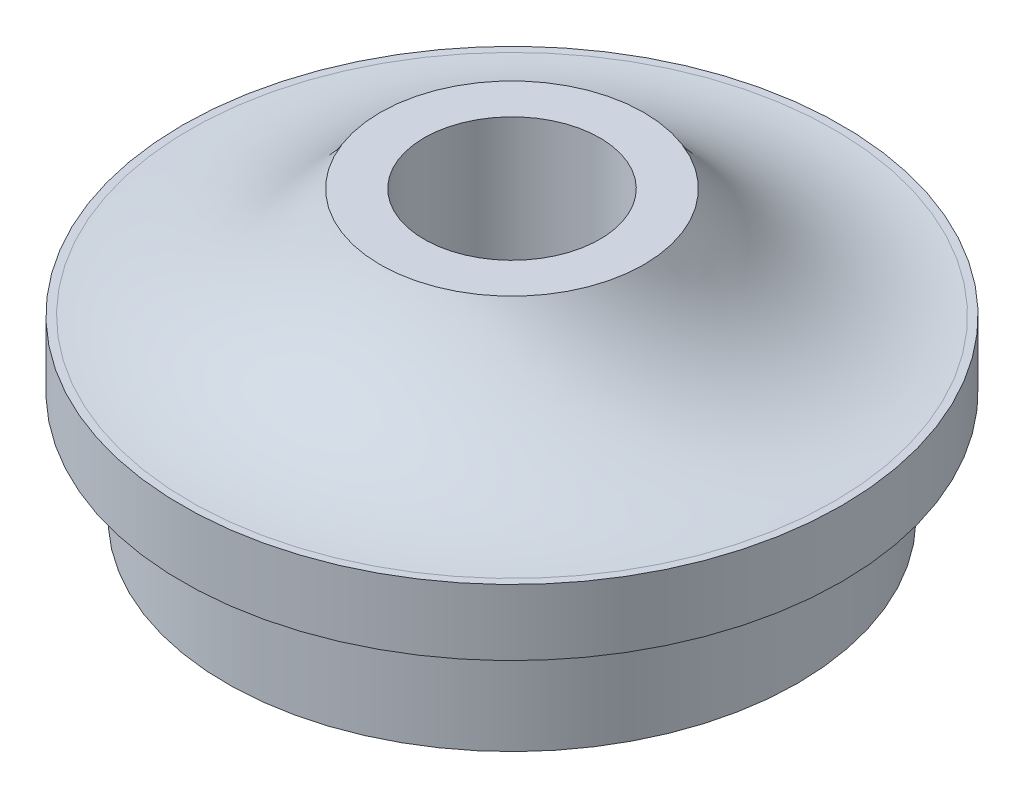
SolidWorks part; units mm, degrees
ref_plane "前视基准面" through (0, 0, 0) normal (0, 0, 1) x (1, 0, 0)
ref_plane "上视基准面" through (0, 0, 0) normal (0, 1, 0) x (1, 0, 0)
ref_plane "右视基准面" through (0, 0, 0) normal (1, 0, 0) x (0, 0, -1)
other "Configuration Table"
sketch "草图1" plane through (0, 0, 0) normal (0, 0, 1) x (1, 0, 0)
  line L0 (0, -267.9145) -> (0, 13127.8098) construction
  line L7 (0, 0) -> (-13, 0)
  line L8 (-13, 0) -> (-13, 5)
  line L9 (-13, 5) -> (-15, 5)
  line L10 (-15, 5) -> (-15, 8)
  line L11 (-15, 8) -> (0, 8)
  line L12 (0, 8) -> (0, 0)
  dimension "D1" = 30
  dimension "D2" = 26
  dimension "D3" = 3
  dimension "D4" = 8
revolve "旋转1" add sketch "草图1" angle 360 about L0
sketch "草图2" plane through (0, 8, 0) normal (0, 1, 0) x (1, 0, 0)
  circle A0 centre (0, 0) radius 6
  dimension "D1" = 12
extrude "凸台-拉伸1" add sketch "草图2" along normal blind 5
fillet "圆角2" radius 10 1 edges at (-6, 8, 0)
sketch "草图3" plane through (0, 13, 0) normal (0, 1, 0) x (1, 0, 0)
  circle A0 centre (0, 0) radius 4
  dimension "D1" = 8
extrude "切除-拉伸1" cut sketch "草图3" against normal blind 18
